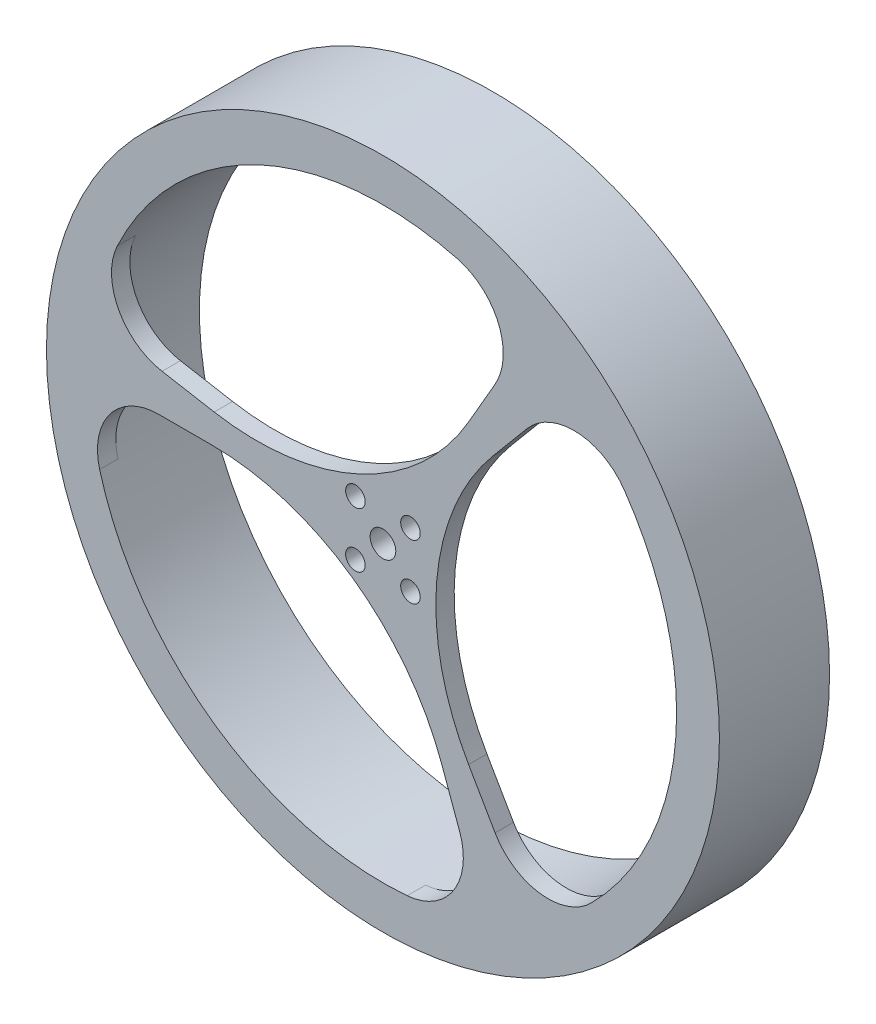
SolidWorks part; units mm, degrees
material "ABS"
ref_plane "Plan de face" through (0, 0, 0) normal (0, 0, 1) x (1, 0, 0)
ref_plane "Plan de dessus" through (0, 0, 0) normal (0, 1, 0) x (1, 0, 0)
ref_plane "Plan de droite" through (0, 0, 0) normal (1, 0, 0) x (0, 0, -1)
sketch "Esquisse1" plane through (0, 0, 0) normal (0, 0, 1) x (1, 0, 0)
  circle A0 centre (0, 0) radius 55
  dimension "D1" = 110
extrude "Boss.-Extru.1" add sketch "Esquisse1" along normal blind 18 contours A0
sketch "Esquisse2" plane through (0, 0, 18) normal (0, 0, 1) x (1, 0, 0)
  circle A1 centre (0, 0) radius 2.1
  dimension "D1" = 4.2
extrude "Enlèv. mat.-Extru.1" cut sketch "Esquisse2" against normal through all
sketch "Esquisse3" plane through (0, 0, 18) normal (0, 0, 1) x (1, 0, 0)
  line L0 (-7.5, 0) -> (-48, 0)
  line L1 (-47.2708, 8.3351) -> (-7.3861, 1.3024)
  line L2 (3.75, 6.4952) -> (24, 41.5692)
  line L3 (4.8209, 5.7453) -> (30.8538, 36.7701)
  line L4 (3.75, -6.4952) -> (24, -41.5692)
  line L5 (16.417, -45.1052) -> (2.5652, -7.0477)
  circle A0 centre (0, 0) radius 48 construction
  circle A1 centre (0, 0) radius 7.5 construction
  arc A2 (-7.5, 0) -> (-7.3861, 1.3024) centre (0, 0) cw
  arc A3 (-48, 0) -> (-47.2708, 8.3351) centre (0, 0) cw
  arc A4 (-7.3861, 1.3024) -> (3.75, 6.4952) centre (0, 0) cw
  arc A5 (-47.2708, 8.3351) -> (24, 41.5692) centre (0, 0) cw
  arc A6 (3.75, 6.4952) -> (4.8209, 5.7453) centre (0, 0) cw
  arc A7 (24, 41.5692) -> (30.8538, 36.7701) centre (0, 0) cw
  arc A8 (4.8209, 5.7453) -> (3.75, -6.4952) centre (0, 0) cw
  arc A9 (30.8538, 36.7701) -> (24, -41.5692) centre (0, 0) cw
  arc A10 (3.75, -6.4952) -> (2.5652, -7.0477) centre (0, 0) cw
  arc A11 (24, -41.5692) -> (16.417, -45.1052) centre (0, 0) cw
  arc A12 (16.417, -45.1052) -> (-48, 0) centre (0, 0) cw
  arc A13 (-7.5, 0) -> (2.5652, -7.0477) centre (0, 0) ccw
  dimension "D1" = 15
  dimension "D2" = 96
extrude "Enlèv. mat.-Extru.2" cut sketch "Esquisse3" against normal through all contours A13 L0 A12 L5 | A5 L1 A4 L2 | A9 L3 A8 L4 region at (-15.9934, -22.8409, 18) region at (-11.7841, 25.2711, 18) region at (27.7775, -2.4302, 18)
sketch "Esquisse7" plane through (0, 0, 0) normal (0, 0, 1) x (1, 0, 0)
  line L1 (2.5652, -7.0477) -> (-27.5317, -39.3193)
  line L2 (-27.5317, -39.3193) -> (-7.5, 0)
  line L4 (4.8209, 5.7453) -> (47.8173, -4.1835)
  line L5 (47.8173, -4.1835) -> (3.75, -6.4952)
  line L7 (3.75, 6.4952) -> (-20.2857, 43.5028)
  line L8 (-20.2857, 43.5028) -> (-7.3861, 1.3024)
  line L9 (3.75, 6.4952) -> (4.8209, 5.7453) construction
  line L10 (2.5652, -7.0477) -> (3.75, -6.4952) construction
  line L11 (-7.5, 0) -> (-7.3861, 1.3024) construction
  line L12 (-2.4674, -3.5238) -> (4.2855, 6.1203) construction
  line L13 (-1.818, 3.8988) -> (3.1576, -6.7714) construction
  line L14 (-7.443, 0.6512) -> (4.2855, -0.3749) construction
  arc A0 (-48, 0) -> (16.417, -45.1052) centre (0, 0) ccw construction
  arc A1 (24, -41.5692) -> (30.8538, 36.7701) centre (0, 0) ccw construction
  arc A2 (24, 41.5692) -> (-47.2708, 8.3351) centre (0, 0) ccw construction
  arc A3 (2.5652, -7.0477) -> (-7.5, 0) centre (4.2855, 6.1203) cw
  arc A4 (-7.3861, 1.3024) -> (3.75, 6.4952) centre (3.1576, -6.7714) cw
  arc A5 (4.8209, 5.7453) -> (3.75, -6.4952) centre (-7.443, 0.6512) cw
extrude "Enlèv. mat.-Extru.3" cut sketch "Esquisse7" along normal through all
sketch "Esquisse8" plane through (0, 0, 0) normal (0, 0, 1) x (1, 0, 0)
  circle A0 centre (0, 0) radius 48
extrude "Enlèv. mat.-Extru.4" cut sketch "Esquisse8" along normal blind 15
fillet "Congé3" radius 10 5 edges at (24, -41.5692, 16.5) (16.417, -45.1052, 16.5) (-48, 0, 16.5) (-47.2708, 8.3351, 16.5) (24, 41.5692, 16.5)
fillet "Congé4" radius 10 1 edges at (30.8538, 36.7701, 16.5)
fillet "Congé5" radius 60 6 edges at (-7.3861, 1.3024, 16.5) (3.75, 6.4952, 16.5) (4.8209, 5.7453, 16.5) (3.75, -6.4952, 16.5) (2.5652, -7.0477, 16.5) (-7.5, 0, 16.5)
fillet "Congé7" radius 40 3 edges at (-2.5497, 5.4679, 16.5) (6.0102, -0.5258, 16.5) (-3.4605, -4.9421, 16.5)
sketch "Esquisse10" plane through (0, 0, 0) normal (0, 0, 1) x (1, 0, 0)
  line L1 (4.5, 4.5) -> (-4.5, 4.5) construction
  line L2 (4.5, 4.5) -> (4.5, -4.5) construction
  line L3 (4.5, -4.5) -> (-4.5, -4.5) construction
  line L4 (-4.5, 4.5) -> (-4.5, -4.5) construction
  line L5 (4.5, 4.5) -> (-4.5, -4.5) construction
  line L6 (4.5, -4.5) -> (-4.5, 4.5) construction
  circle A8 centre (-4.5, -4.5) radius 1.6
  circle A9 centre (-4.5, 4.5) radius 1.6
  circle A10 centre (4.5, 4.5) radius 1.6
  circle A11 centre (4.5, -4.5) radius 1.6
  point P0 (0, 0)
  point P14 (0, 0)
  point P15 (0, 0)
  point P19 (0, 0)
  dimension "D1" = 9
  dimension "D2" = 9
  dimension "D3" = 3.2
  dimension "D4" = 4
extrude "Enlèv. mat.-Extru.9" cut sketch "Esquisse10" along normal through all
